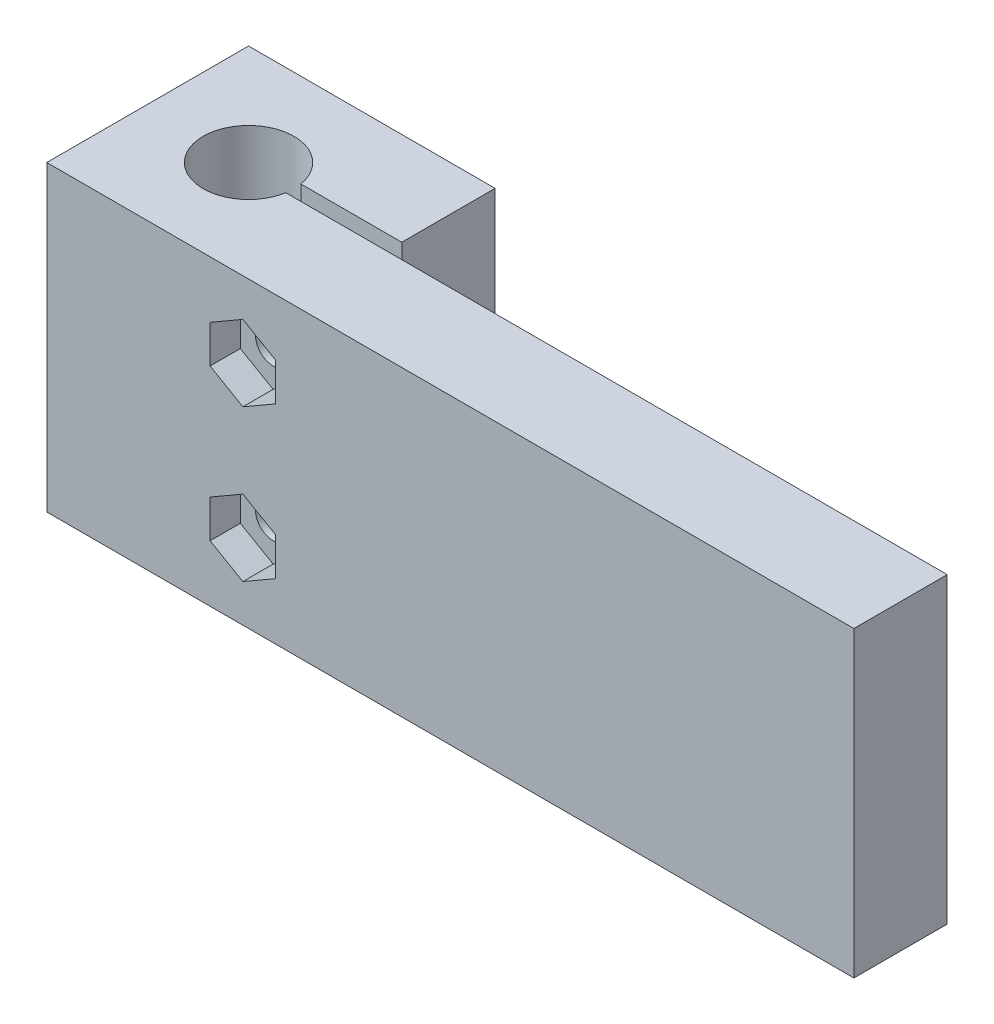
SolidWorks part; units mm, degrees
ref_plane "Piano frontale" through (0, 0, 0) normal (0, 0, 1) x (1, 0, 0)
ref_plane "Piano superiore" through (0, 0, 0) normal (0, 1, 0) x (1, 0, 0)
ref_plane "Piano destro" through (0, 0, 0) normal (1, 0, 0) x (0, 0, -1)
sketch "Schizzo2" plane through (0, 0, 0) normal (0, 1, 0) x (1, 0, 0)
  line L0 (0, 0) -> (0, 20)
  line L1 (0, 20) -> (24.4371, 20)
  line L2 (24.4371, 20) -> (24.4371, 10.75)
  line L3 (0, 0) -> (80, 0)
  line L4 (24.4371, 10.75) -> (14.4371, 10.75)
  line L5 (14.4371, 9.25) -> (80, 9.25)
  line L6 (10, 20) -> (10, 0) construction
  line L7 (80, 0) -> (80, 9.25)
  arc A0 (14.4371, 10.75) -> (14.4371, 9.25) centre (10, 10) ccw
  dimension "D1" = 4.5
  dimension "D2" = 20
  dimension "D3" = 10
  dimension "D4" = 1.5
  dimension "D5" = 10
  dimension "D6" = 80
extrude "Main Body" add sketch "Schizzo2" along normal mid plane 30
sketch "Schizzo3" plane through (0, 0, -20) normal (0, 0, -1) x (-1, 0, 0)
  line L0 (-14.4371, 15) -> (-14.4371, -15) construction
  line L1 (-14.4371, 15) -> (-14.4371, -15) construction
  line L2 (-24.4371, -7.5) -> (-14.4371, -7.5) construction
  line L3 (-24.4371, 15) -> (-24.4371, -15) construction
  line L4 (-24.4371, 7.5) -> (-14.4371, 7.5) construction
  line L5 (-24.4371, 0) -> (0, 0) construction
  line L6 (0, 15) -> (0, -15) construction
  line L7 (-20.4474, -5.75) -> (-18.4267, -5.75)
  line L8 (-20.4474, 9.25) -> (-18.4267, 9.25)
  line L9 (-20.4474, -5.75) -> (-20.9526, -6.625)
  line L10 (-18.4267, -5.75) -> (-17.9215, -6.625)
  line L11 (-18.4267, 9.25) -> (-17.9215, 8.375)
  line L12 (-20.4474, 9.25) -> (-20.9526, 8.375)
  line L13 (-19.4371, 0) -> (-19.4371, -15) construction
  line L14 (-24.4371, -15) -> (0, -15) construction
  line L15 (-19.4371, 0) -> (-19.4371, 15) construction
  line L16 (-24.4371, 15) -> (0, 15) construction
  arc A0 (-20.9526, -6.625) -> (-17.9215, -6.625) centre (-19.4371, -7.5) ccw
  arc A1 (-20.9526, 8.375) -> (-17.9215, 8.375) centre (-19.4371, 7.5) ccw
  point P19 (-19.4371, -5.75)
  point P22 (-19.4371, 9.25)
  dimension "D1" = 3.5
  dimension "D2" = 120
  dimension "D3" = 120
extrude "Holes" cut sketch "Schizzo3" against normal through all
sketch "Schizzo4" plane through (0, 0, 0) normal (0, 0, 1) x (1, 0, 0)
  line L1 (19.4371, 11.2528) -> (16.1871, 9.3764)
  line L2 (16.1871, 9.3764) -> (16.1871, 5.6236)
  line L3 (16.1871, 5.6236) -> (19.4371, 3.7472)
  line L4 (19.4371, 3.7472) -> (22.6871, 5.6236)
  line L5 (22.6871, 5.6236) -> (22.6871, 9.3764)
  line L6 (22.6871, 9.3764) -> (19.4371, 11.2528)
  line L7 (19.4371, -3.7472) -> (16.1871, -5.6236)
  line L8 (16.1871, -5.6236) -> (16.1871, -9.3764)
  line L9 (16.1871, -9.3764) -> (19.4371, -11.2528)
  line L10 (19.4371, -11.2528) -> (22.6871, -9.3764)
  line L11 (22.6871, -9.3764) -> (22.6871, -5.6236)
  line L12 (22.6871, -5.6236) -> (19.4371, -3.7472)
  arc A0 (17.9215, 8.375) -> (20.9526, 8.375) centre (19.4371, 7.5) ccw construction
  arc A1 (17.9215, -6.625) -> (20.9526, -6.625) centre (19.4371, -7.5) ccw construction
  arc A2 (17.9215, 8.375) -> (20.9526, 8.375) centre (19.4371, 7.5) ccw construction
  arc A3 (17.9215, -6.625) -> (20.9526, -6.625) centre (19.4371, -7.5) ccw construction
  circle A4 centre (19.4371, 7.5) radius 3.25 construction
  circle A5 centre (19.4371, -7.5) radius 3.25 construction
  dimension "D1" = 6.5
extrude "Hex nut recess" cut sketch "Schizzo4" against normal blind 3
ref_axis "Shaft axis" through (10, 15, -10) along (0, -1, 0)
ref_axis "Screw hole 1" through (19.4371, 7.5, -10.75) along (0, 0, -1)
ref_axis "Screw hole 2" through (19.4371, -7.5, -10.75) along (0, 0, -1)
